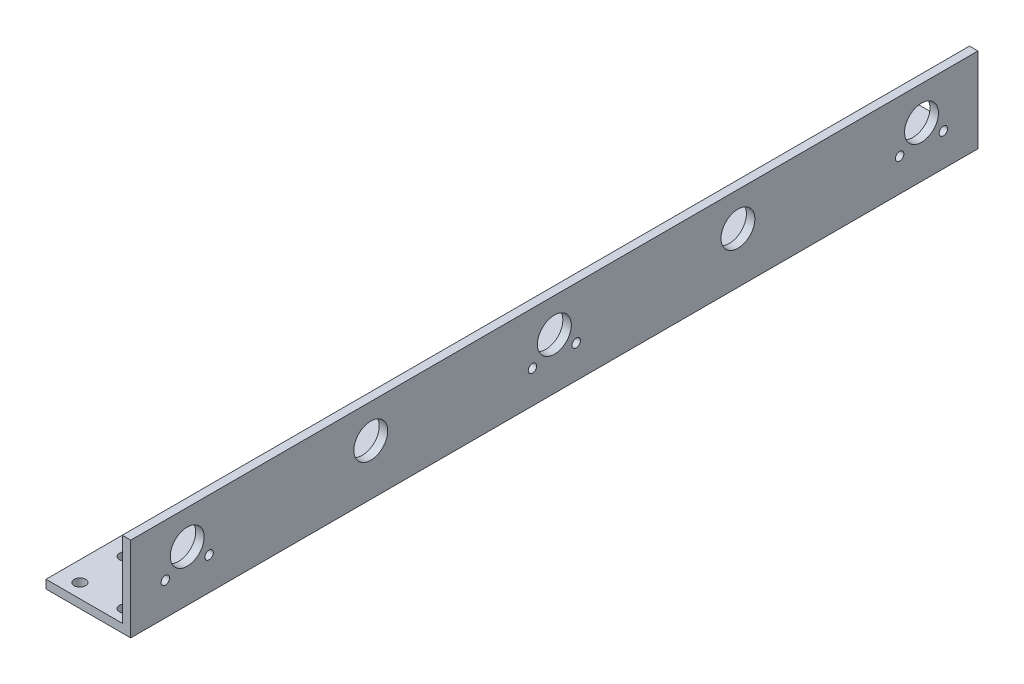
SolidWorks part; units mm, degrees
ref_plane "Front" through (0, 0, 0) normal (0, 0, 1) x (1, 0, 0)
ref_plane "Top" through (0, 0, 0) normal (0, 1, 0) x (1, 0, 0)
ref_plane "Right" through (0, 0, 0) normal (1, 0, 0) x (0, 0, -1)
sketch "草图1" plane through (0, 0, 0) normal (0, 0, 1) x (1, 0, 0)
  line L1 (-15, -15) -> (15, -15)
  line L2 (-15, -15) -> (-15, -12)
  line L3 (12, 15) -> (15, 15)
  line L4 (15, -15) -> (15, 15)
  line L8 (12, 15) -> (12, -12)
  line L9 (-15, -12) -> (12, -12)
  point P0 (0, 0)
extrude "凸台-拉伸1" add sketch "草图1" along normal blind 300
sketch "草图2" plane through (12, 0, 0) normal (-1, 0, 0) x (0, 0, 1)
  circle A0 centre (20, 3) radius 6
  circle A1 centre (85, 3) radius 6
  circle A2 centre (150, 3) radius 6
  circle A3 centre (215, 3) radius 6
  circle A4 centre (280, 3) radius 6
  dimension "D1" = 5
extrude "切除-拉伸1" cut sketch "草图2" against normal blind 300
sketch "草图3" plane through (0, -15, 0) normal (0, -1, 0) x (1, 0, 0)
  line L0 (0, 300) -> (0, 295)
  line L2 (-15, 300) -> (15, 300) construction
  circle A0 centre (8, 5) radius 2
  circle A1 centre (-8, 5) radius 2
  circle A2 centre (-8, 21) radius 2
  circle A3 centre (8, 21) radius 2
  circle A4 centre (8, 295) radius 2
  circle A5 centre (8, 279) radius 2
  circle A6 centre (-8, 279) radius 2
  circle A7 centre (-8, 295) radius 2
  point P21 (0, 13)
  point P30 (0, 287)
  dimension "D1" = 4
  dimension "D2" = 4
extrude "切除-拉伸2" cut sketch "草图3" against normal blind 300 contours A7 | A6 | A5 | A4 | A2 | A1 | A0 | A3 region at (8, -15, 5) region at (-8, -15, 5) region at (-8, -15, 21) region at (8, -15, 21) region at (8, -15, 295) region at (8, -15, 279) region at (-8, -15, 279) region at (-8, -15, 295)
sketch "草图4" plane through (15, 0, 0) normal (1, 0, 0) x (0, 0, -1)
  circle A2 centre (-27.75, -3.4234) radius 1.5
  circle A5 centre (-12.25, -3.4234) radius 1.5
  circle A10 centre (-272.25, -3.4234) radius 1.5
  circle A11 centre (-287.75, -3.4234) radius 1.5
  circle A13 centre (-142.25, -3.4234) radius 1.5
  circle A14 centre (-157.75, -3.4234) radius 1.5
  point P18 (-20, 10)
extrude "切除-拉伸3" cut sketch "草图4" against normal blind 10
